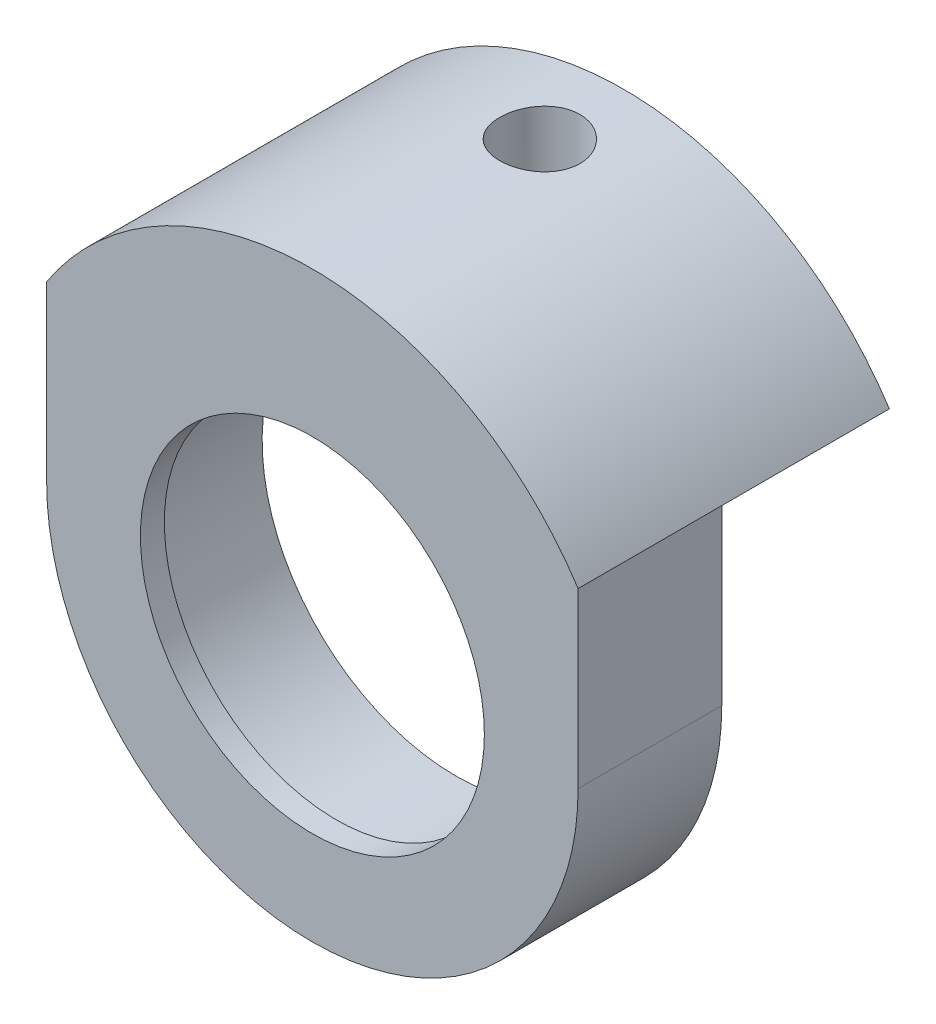
SolidWorks part; units mm, degrees
ref_plane "Front Plane" through (0, 0, 0) normal (0, 0, 1) x (1, 0, 0)
ref_plane "Top Plane" through (0, 0, 0) normal (0, 1, 0) x (1, 0, 0)
ref_plane "Right Plane" through (0, 0, 0) normal (1, 0, 0) x (0, 0, -1)
sketch "Sketch1" plane through (0, 0, 0) normal (0, 0, 1) x (1, 0, 0)
  line L0 (-11.1, 0) -> (11.1, 0)
  line L1 (-11.1, 0) -> (-11.1, 7.2355)
  line L2 (11.1, 0) -> (11.1, 7.2355)
  circle A0 centre (0, 0) radius 8.1
  circle A1 centre (0, 0) radius 13.25
  circle A2 centre (0, 0) radius 11.1
  dimension "16.2" = 16.2
  dimension "D2" = 26.5
  dimension "D3" = 3
extrude "Boss-Extrude1" add sketch "Sketch1" along normal blind 13 contours L0 A2 A0 | A2 L2 A1 L1 | L0 A2 A0 region at (0, 8.3482, 0) region at (9.6, -0.2482, 0) region at (0, 11.3585, 0)
sketch "Sketch2" plane through (-11.1, 0, 0) normal (-1, 0, 0) x (0, 0, 1)
  line L0 (13, 0) -> (13, 7.2355) construction
  line L1 (0, 7.2355) -> (7, 7.2355)
  line L2 (0, 7.2355) -> (0, -11.1)
  line L3 (0, -11.1) -> (7, -11.1)
  line L4 (7, 7.2355) -> (7, -11.1)
  dimension "D1" = 6
extrude "Cut-Extrude1" cut sketch "Sketch2" against normal up to surface (22.2 mm away) up to face at (11.1, 3.6178, 6.5)
sketch "Sketch3" plane through (0, 7.2355, 0) normal (0, -1, 0) x (1, 0, 0)
  line L0 (-3.6411, 0) -> (3.6411, 0) construction
  circle A0 centre (0, 3.5) radius 1.675
  dimension "D1" = 3.35
  dimension "D2" = 3.5
extrude "Cut-Extrude2" cut sketch "Sketch3" against normal up to surface (5.9082 mm away) up to face at (0, 9.2403, 6.6667)
sketch "Sketch4" plane through (0, 7.2355, 0) normal (0, -1, 0) x (1, 0, 0)
  line L1 (2.775, 5.1021) -> (0, 6.7043)
  line L2 (0, 6.7043) -> (-2.775, 5.1021)
  line L3 (-2.775, 5.1021) -> (-2.775, 1.8979)
  line L4 (-2.775, 1.8979) -> (0, 0.2957)
  line L5 (0, 0.2957) -> (2.775, 1.8979)
  line L6 (2.775, 1.8979) -> (2.775, 5.1021)
  line L7 (-3.6411, 0) -> (-3.6411, 7) construction
  circle A0 centre (0, 3.5) radius 2.775 construction
  dimension "5.55" = 5.55
extrude "Cut-Extrude3" cut sketch "Sketch4" against normal blind 2.2
sketch "Sketch5" plane through (0, 0, 13) normal (0, 0, 1) x (1, 0, 0)
  circle A0 centre (0, 0) radius 8.1835
  circle A1 centre (0, 0) radius 7.1835
  dimension "D1" = 1
extrude "Boss-Extrude2" add sketch "Sketch5" against normal blind 1
